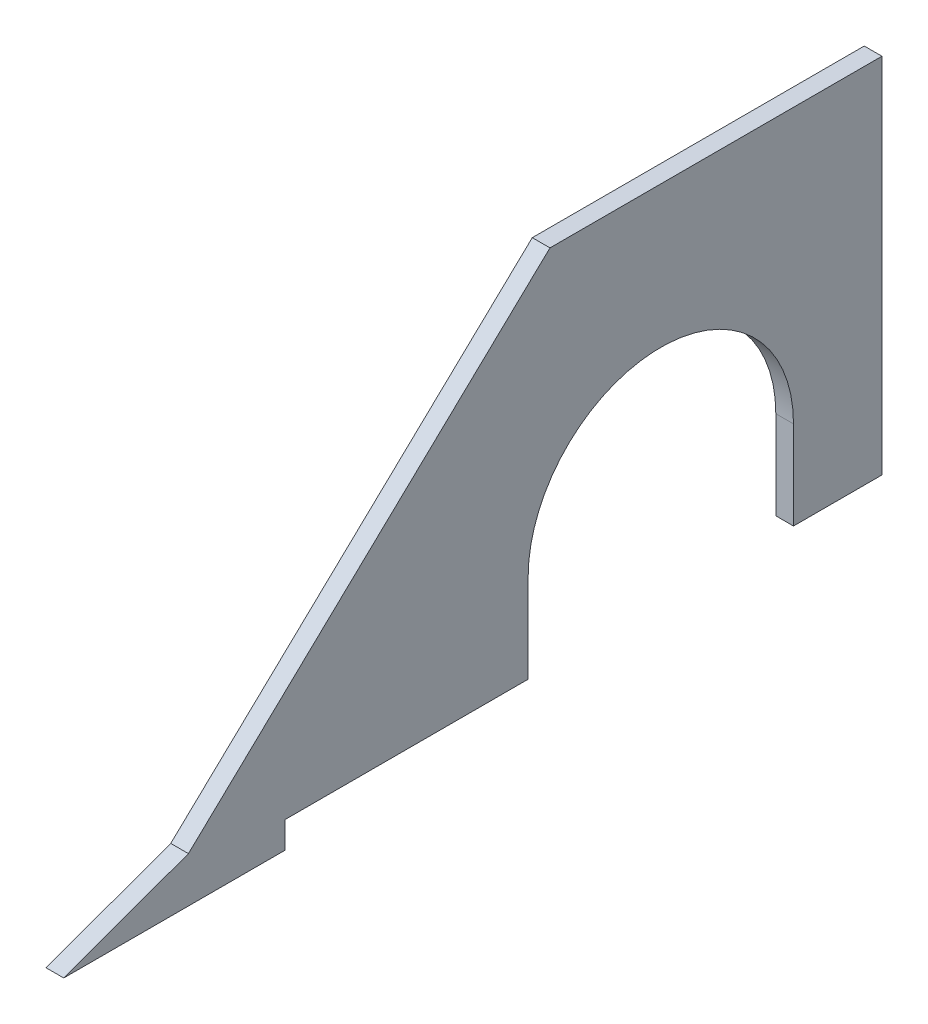
SolidWorks part; units mm, degrees
ref_plane "Alzado" through (0, 0, 0) normal (0, 0, 1) x (1, 0, 0)
ref_plane "Planta" through (0, 0, 0) normal (0, 1, 0) x (1, 0, 0)
ref_plane "Vista lateral" through (0, 0, 0) normal (1, 0, 0) x (0, 0, -1)
sketch "Croquis1" plane through (0, 0, 0) normal (1, 0, 0) x (0, 0, -1)
  line L0 (0, 0) -> (28.1908, 10.2606)
  line L2 (50, 0) -> (0, 0)
  line L4 (50, 0) -> (50, 6)
  line L5 (50, 6) -> (185, 6)
  line L6 (185, 6) -> (185, 88)
  line L7 (185, 88) -> (109.9403, 88)
  line L8 (109.9403, 88) -> (28.1908, 10.2606)
  line L9 (50, 6) -> (50, 31) construction
  dimension "D1" = 20
  dimension "D2" = 50
  dimension "D3" = 135
  dimension "D4" = 6
  dimension "D5" = 25
  dimension "D6" = 82
  dimension "D7" = 30
extrude "Saliente-Extruir2" add sketch "Croquis1" along normal blind 4
sketch "Croquis2" plane through (4, 0, 0) normal (1, 0, 0) x (0, 0, -1)
  line L0 (135, 6) -> (135, 63.4974) construction
  line L1 (50, 6) -> (185, 6) construction
  line L2 (185, 6) -> (185, 88) construction
  line L8 (105, 6) -> (165, 6)
  line L9 (105, 6) -> (105, 26)
  line L11 (165, 6) -> (165, 26)
  arc A2 (165, 26) -> (105, 26) centre (135, 26) ccw
  dimension "D2" = 30
  dimension "D3" = 60
  dimension "D4" = 20
  dimension "D1" = 50
extrude "Cortar-Extruir1" cut sketch "Croquis2" against normal blind 4
